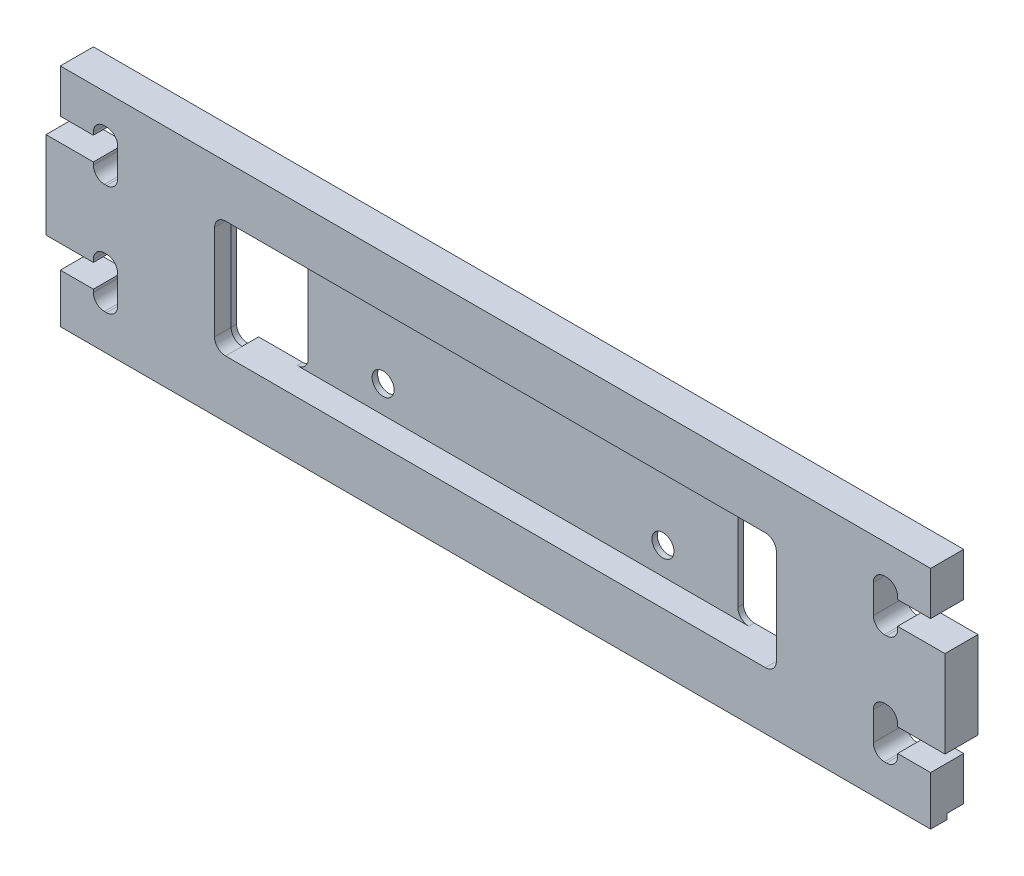
SolidWorks part; units mm, degrees
note: '?' marks a value the reader was unsure of.
ref_plane "Front Plane" through (0, 0, 0) normal (0, 0, 1) x (1, 0, 0)
ref_plane "Top Plane" through (0, 0, 0) normal (0, 1, 0) x (1, 0, 0)
ref_plane "Right Plane" through (0, 0, 0) normal (1, 0, 0) x (0, 0, -1)
sketch "Sketch1" plane through (0, 0, 0) normal (0, 0, 1) x (1, 0, 0)
  line L0 (-39.5, 0) -> (39.5, 0) construction
  line L1 (-39.5, 10) -> (39.5, 10)
  line L2 (-39.5, 10) -> (-39.5, -10)
  line L3 (-39.5, -10) -> (39.5, -10)
  line L4 (39.5, 10) -> (39.5, -10)
  line L5 (-39.5, 10) -> (39.5, -10) construction
  line L6 (-39.5, -10) -> (39.5, 10) construction
  line L7 (0, 10) -> (0, -10) construction
  line L9 (-40.8, -3.95) -> (-39.5, -3.95)
  line L10 (-40.8, -3.95) -> (-40.8, 3.95)
  line L11 (-40.8, 3.95) -> (-39.5, 3.95)
  line L12 (-39.5, -3.95) -> (-39.5, 3.95)
  line L13 (-40.8, -3.95) -> (-39.5, 3.95) construction
  line L14 (-40.8, 3.95) -> (-39.5, -3.95) construction
  line L16 (40.8, 3.95) -> (39.5, 3.95)
  line L17 (40.8, -3.95) -> (40.8, 3.95)
  line L18 (40.8, -3.95) -> (39.5, -3.95)
  line L19 (-39.5, 5) -> (39.5, 5) construction
  line L20 (-35.4, 7.3) -> (-35.4, 2.7) construction
  line L21 (-36.5, 3.95) -> (-39.5, 3.95)
  line L22 (-36.5, 3.95) -> (-36.5, 6.05)
  line L23 (-36.5, 6.05) -> (-39.5, 6.05)
  line L24 (-39.5, 3.95) -> (-39.5, 6.05)
  line L25 (-36.5, 3.95) -> (-39.5, 6.05) construction
  line L26 (-36.5, 6.05) -> (-39.5, 3.95) construction
  line L27 (-34.3, 7.3) -> (-36.5, 7.3)
  line L28 (-34.3, 7.3) -> (-34.3, 2.7)
  line L29 (-34.3, 2.7) -> (-36.5, 2.7)
  line L30 (-36.5, 7.3) -> (-36.5, 2.7)
  line L31 (-34.3, 7.3) -> (-36.5, 2.7) construction
  line L32 (-34.3, 2.7) -> (-36.5, 7.3) construction
  line L33 (-34.3, -7.3) -> (-36.5, -7.3)
  line L34 (-34.3, -7.3) -> (-34.3, -2.7)
  line L35 (-34.3, -2.7) -> (-36.5, -2.7)
  line L36 (-36.5, -7.3) -> (-36.5, -2.7)
  line L37 (-36.5, -3.95) -> (-39.5, -3.95)
  line L38 (-36.5, -6.05) -> (-39.5, -6.05)
  line L39 (36.5, 3.95) -> (39.5, 3.95)
  line L40 (36.5, 6.05) -> (39.5, 6.05)
  line L41 (36.5, 7.3) -> (36.5, 2.7)
  line L42 (34.3, 7.3) -> (36.5, 7.3)
  line L43 (34.3, 7.3) -> (34.3, 2.7)
  line L44 (34.3, 2.7) -> (36.5, 2.7)
  line L45 (34.3, -2.7) -> (36.5, -2.7)
  line L46 (34.3, -7.3) -> (34.3, -2.7)
  line L47 (34.3, -7.3) -> (36.5, -7.3)
  line L48 (36.5, -7.3) -> (36.5, -2.7)
  line L49 (36.5, -6.05) -> (39.5, -6.05)
  line L50 (36.5, -3.95) -> (39.5, -3.95)
  point P0 (0, 0)
  point P10 (-40.15, 0)
  point P15 (-38, 5)
  point P35 (-35.4, 5)
  dimension "D1" = 79
  dimension "D2" = 20
  dimension "D4" = 1.3
  dimension "D7" = 5
  dimension "D8" = 2.1
  dimension "D9" = 3
  dimension "D10" = 2.2
  dimension "D11" = 4.6
extrude "Base shape" add sketch "Sketch1" along normal blind 3
sketch "Sketch4" plane through (0, -10, 0) normal (0, -1, 0) x (1, 0, 0)
  line L0 (39.5, 3) -> (39.5, 0) construction
  line L1 (-39.5, 3) -> (39.5, 3)
  line L2 (-39.5, 3) -> (-39.5, 1.5)
  line L3 (-39.5, 1.5) -> (39.5, 1.5)
  line L4 (39.5, 3) -> (39.5, 1.5)
extrude "Floor lip" add sketch "Sketch4" along normal blind 0.5
sketch "Sketch6" plane through (0, 0, 0) normal (0, 0, -1) x (-1, 0, 0)
  line L0 (0, 0) -> (0, -10) construction
  line L1 (39.5, -10) -> (-39.5, -10) construction
  line L2 (-4, -10) -> (4, -10) construction
  line L3 (39.5, -10) -> (-39.5, -10) construction
  line L4 (-4, -9) -> (4, -9)
  line L5 (-4, -11) -> (4, -11)
  arc A0 (-4, -9) -> (-4, -11) centre (-4, -10) ccw
  arc A1 (4, -11) -> (4, -9) centre (4, -10) ccw
  point P9 (0, -10)
  dimension "D1" = 2
  dimension "D2" = 8
extrude "Nail cutout" cut sketch "Sketch6" against normal up to surface (1.5 mm away) up to face at (0, -10.25, 1.5)
sketch "Tap axis sketch" plane through (-40.8, 0, 0) normal (-1, 0, 0) x (0, 0, 1)
  line L0 (0, 6.05) -> (3, 3.95) construction
  line L1 (0, 6.05) -> (3, 6.05)
  line L2 (0, 6.05) -> (0, 3.95)
  line L3 (0, 3.95) -> (3, 3.95)
  line L4 (3, 6.05) -> (3, 3.95)
  line L5 (0, -3.95) -> (3, -6.05) construction
  line L6 (0, -3.95) -> (3, -3.95)
  line L7 (0, -3.95) -> (0, -6.05)
  line L8 (0, -6.05) -> (3, -6.05)
  line L9 (3, -3.95) -> (3, -6.05)
  point P6 (1.5, 5)
  point P13 (1.5, -5)
ref_axis "Tap axis top" through (-53.7846, 5, 1.5) along (1, 0, 0)?
ref_axis "Tap axis bottom" through (-54.2844, -5, 1.5) along (1, 0, 0)?
fillet "Mill fillets" radius 1 16 edges at (36.5, -7.3, 1.5) (36.5, 2.7, 1.5) (34.3, 2.7, 1.5) (34.3, -7.3, 1.5) (36.5, -2.7, 1.5) (36.5, 7.3, 1.5) (34.3, -2.7, 1.5) (34.3, 7.3, 1.5) (-36.5, -2.7, 1.5) (-34.3, -2.7, 1.5) (-34.3, -7.3, 1.5) (-36.5, -7.3, 1.5) (-36.5, 2.7, 1.5) (-34.3, 2.7, 1.5) (-34.3, 7.3, 1.5) (-36.5, 7.3, 1.5)
sketch "Sketch8" plane through (0, 0, 3) normal (0, 0, 1) x (1, 0, 0)
  line L0 (-40.8, 0) -> (40.8, 0) construction
  line L1 (-40.8, -3.95) -> (-40.8, 3.95) construction
  line L2 (40.8, -3.95) -> (40.8, 3.95) construction
  line L4 (-24.5, 5.3) -> (24.5, 5.3)
  line L5 (-25.5, 4.3) -> (-25.5, -4.3)
  line L6 (-24.5, -5.3) -> (24.5, -5.3)
  line L7 (25.5, 4.3) -> (25.5, -4.3)
  line L8 (-25.5, 5.3) -> (25.5, -5.3) construction
  line L9 (-25.5, -5.3) -> (25.5, 5.3) construction
  arc A0 (24.5, -5.3) -> (25.5, -4.3) centre (24.5, -4.3) ccw
  arc A1 (24.5, 5.3) -> (25.5, 4.3) centre (24.5, 4.3) cw
  arc A2 (-25.5, -4.3) -> (-24.5, -5.3) centre (-24.5, -4.3) ccw
  arc A3 (-24.5, 5.3) -> (-25.5, 4.3) centre (-24.5, 4.3) ccw
  point P6 (0, 0)
  dimension "D3" = 1
  dimension "D1" = 51
  dimension "D2" = 10.6
extrude "Led strip pocket" cut sketch "Sketch8" against normal offset from surface (2.5 mm away) 0.5 up to face at (0, -0.6712, 0)
sketch "Sketch9" plane through (0, 0, 0.5) normal (0, 0, 1) x (1, 0, 0)
  line L0 (-19.5, 5.3) -> (-19.5, -5.3)
  line L1 (0, 5.3) -> (0, -5.3) construction
  line L2 (19.5, 5.3) -> (19.5, -5.3)
  line L3 (-25.5, -2.828) -> (25.5, -2.828) construction
  line L4 (25.5, -4.3) -> (25.5, 4.3)
  line L5 (24.5, 5.3) -> (-24.5, 5.3)
  line L6 (-25.5, 4.3) -> (-25.5, -4.3)
  line L7 (-24.5, -5.3) -> (24.5, -5.3)
  line L8 (25.5, -4.3) -> (25.5, 4.3)
  line L9 (24.5, 5.3) -> (-24.5, 5.3)
  line L10 (-25.5, 4.3) -> (-25.5, -4.3)
  line L11 (-24.5, -5.3) -> (24.5, -5.3)
  circle A0 centre (-12.7, -2.828) radius 1
  circle A1 centre (12.7, -2.828) radius 1
  arc A4 (24.5, -5.3) -> (25.5, -4.3) centre (24.5, -4.3) ccw
  arc A5 (25.5, 4.3) -> (24.5, 5.3) centre (24.5, 4.3) ccw
  arc A6 (-24.5, 5.3) -> (-25.5, 4.3) centre (-24.5, 4.3) ccw
  arc A7 (-25.5, -4.3) -> (-24.5, -5.3) centre (-24.5, -4.3) ccw
  arc A8 (24.5, -5.3) -> (25.5, -4.3) centre (24.5, -4.3) ccw
  arc A9 (25.5, 4.3) -> (24.5, 5.3) centre (24.5, 4.3) ccw
  arc A10 (-24.5, 5.3) -> (-25.5, 4.3) centre (-24.5, 4.3) ccw
  arc A11 (-25.5, -4.3) -> (-24.5, -5.3) centre (-24.5, -4.3) ccw
  arc M13 (24.5, -5.3) -> (25.5, -4.3) centre (24.5, -4.3) ccw
  line M14 (25.5, -4.3) -> (25.5, 4.3)
  arc M15 (25.5, 4.3) -> (24.5, 5.3) centre (24.5, 4.3) ccw
  line M16 (24.5, 5.3) -> (-24.5, 5.3)
  arc M17 (-24.5, 5.3) -> (-25.5, 4.3) centre (-24.5, 4.3) ccw
  line M18 (-25.5, 4.3) -> (-25.5, -4.3)
  arc M19 (-25.5, -4.3) -> (-24.5, -5.3) centre (-24.5, -4.3) ccw
  line M20 (-24.5, -5.3) -> (24.5, -5.3)
  dimension "D4" = 2
  dimension "D2" = 6
  dimension "D3" = 8.128
  dimension "D5" = 25.4
  dimension "D1" = 0
extrude "Led strip cuts" cut sketch "Sketch9" against normal up to next contours L0 M16 M17 M18 M19 M20 | L2 M16 M20 M13 M14 M15 | A0 | A1
fillet "Led strip cut fillets" radius 1 4 edges at (19.5, -5.3, 0.25) (19.5, 5.3, 0.25) (-19.5, -5.3, 0.25) (-19.5, 5.3, 0.25)
sketch "Sketch23" plane through (0, 0, 0) normal (0, 0, -1) x (-1, 0, 0)
  line L0 (0, 12.1767) -> (0, -13.8681) construction
  line L1 (-25.5, -5.3) -> (-25.5, 5.3) construction
  line L2 (-25.5, 4.3) -> (-25.5, -4.3) construction
  line L3 (-26.5, -5.3) -> (-26.5, 5.3)
  line L4 (-24.5, -5.3) -> (-24.5, 5.3)
  line L5 (-20.5, 5.3) -> (-24.5, 5.3) construction
  line L6 (25.5, -5.3) -> (25.5, 5.3) construction
  line L7 (26.5, -5.3) -> (26.5, 5.3)
  line L8 (24.5, -5.3) -> (24.5, 5.3)
  arc A0 (-26.5, -5.3) -> (-24.5, -5.3) centre (-25.5, -5.3) ccw
  arc A1 (-24.5, 5.3) -> (-26.5, 5.3) centre (-25.5, 5.3) ccw
  arc A2 (26.5, -5.3) -> (24.5, -5.3) centre (25.5, -5.3) cw
  arc A3 (24.5, 5.3) -> (26.5, 5.3) centre (25.5, 5.3) cw
  point P7 (-25.5, 0)
  point P18 (25.5, 0)
  dimension "D1" = 2
extrude "LED PCB pads clearance slots" cut sketch "Sketch23" against normal blind 1.5
sketch "Sketch13" plane through (0, 0, 0) normal (0, 0, -1) x (-1, 0, 0)
  line L0 (0, 15.8648) -> (0, -21.9195) construction
  line L2 (-4.2, -6.3) -> (4.2, -6.3)
  line L3 (-5.2, -5.3) -> (-5.2, 6)
  line L4 (-4.2, 7) -> (4.2, 7)
  line L5 (5.2, -5.3) -> (5.2, 6)
  line L6 (-5.2, -6.3) -> (5.2, 7) construction
  line L7 (-5.2, 7) -> (5.2, -6.3) construction
  line L10 (39.5, 10) -> (-39.5, 10) construction
  arc A0 (-4.2, -6.3) -> (-5.2, -5.3) centre (-4.2, -5.3) cw
  arc A1 (4.2, -6.3) -> (5.2, -5.3) centre (4.2, -5.3) ccw
  arc A4 (5.2, 6) -> (4.2, 7) centre (4.2, 6) ccw
  arc A5 (-5.2, 6) -> (-4.2, 7) centre (-4.2, 6) cw
  point P1 (0, 0.35)
  dimension "D4" = 1
  dimension "D5" = 1
  dimension "D1" = 10.4
  dimension "D2" = 13.3
  dimension "D3" = 3
extrude "Bumper mount inner cut" [suppressed] cut sketch "Sketch13" against normal offset from surface (2.6 mm away) 0.4
sketch "Sketch14" [suppressed] plane through (0, 0, 0) normal (0, 0, -1) x (-1, 0, 0)
  line L1 (0, 12.9528) -> (0, -14.0841) construction
  line L2 (4.2, 7) -> (-4.2, 7) construction
  line L3 (-4.2, -6.3) -> (4.2, -6.3) construction
  line L4 (-11.7, 7) -> (11.7, 7)
  line L5 (-12.7, 6) -> (-12.7, -5.3)
  line L6 (-11.7, -6.3) -> (11.7, -6.3)
  line L7 (12.7, 6) -> (12.7, -5.3)
  line L8 (-12.7, 7) -> (12.7, -6.3) construction
  line L9 (-12.7, -6.3) -> (12.7, 7) construction
  arc A1 (11.7, -6.3) -> (12.7, -5.3) centre (11.7, -5.3) ccw
  arc A2 (-12.7, -5.3) -> (-11.7, -6.3) centre (-11.7, -5.3) ccw
  arc A3 (11.7, 7) -> (12.7, 6) centre (11.7, 6) cw
  arc A4 (-12.7, 6) -> (-11.7, 7) centre (-11.7, 6) cw
  point P6 (0, 0.35)
  dimension "D2" = 1
  dimension "D3" = 1
  dimension "D1" = 25.4
extrude "Bumper mount outer cut" [suppressed] cut sketch "Sketch14" against normal blind 1.6
sketch "Sketch15" [suppressed] plane through (0, 0, 1.6) normal (0, 0, -1) x (-1, 0, 0)
  line L0 (-12.7, 2.8) -> (12.7, 2.8) construction
  line L3 (0, 16.4744) -> (0, -20.0474) construction
  line L7 (-12.7, 6) -> (-12.7, -5.3) construction
  line L8 (12.7, -5.3) -> (12.7, 6) construction
  line L11 (-4.2, 7) -> (-11.7, 7) construction
  circle A0 centre (-9, 2.8) radius 1
  circle A1 centre (9, 2.8) radius 1
  dimension "D1" = 18
  dimension "D2" = 2
  dimension "D3" = 4.2
extrude "Bumper mount screw holes" [suppressed] cut sketch "Sketch15" against normal up to next
sketch "Sketch16" [suppressed] plane through (0, 0, 2.6) normal (0, 0, -1) x (-1, 0, 0)
  line L0 (-5.2, 1.1) -> (5.2, 1.1) construction
  line L3 (0, 7) -> (0, -4.8) construction
  line L4 (-2.5, 3) -> (2.5, 3)
  line L5 (-3.5, 2) -> (-3.5, 0.2)
  line L6 (-2.5, -0.8) -> (2.5, -0.8)
  line L7 (3.5, 2) -> (3.5, 0.2)
  line L8 (-3.5, 3) -> (3.5, -0.8) construction
  line L9 (-3.5, -0.8) -> (3.5, 3) construction
  line L11 (-5.2, 6) -> (-5.2, -5.3) construction
  line L13 (4.2, 7) -> (-4.2, 7) construction
  arc A0 (2.5, -0.8) -> (3.5, 0.2) centre (2.5, 0.2) ccw
  arc A1 (-3.5, 0.2) -> (-2.5, -0.8) centre (-2.5, 0.2) ccw
  arc A2 (-2.5, 3) -> (-3.5, 2) centre (-2.5, 2) ccw
  arc A3 (2.5, 3) -> (3.5, 2) centre (2.5, 2) cw
  point P6 (0, 1.1)
  dimension "D3" = 1
  dimension "D1" = 7
  dimension "D2" = 3.8
  dimension "D4" = 11.8
extrude "Bumper body cut" [suppressed] cut sketch "Sketch16" against normal up to next
hole_wizard "Bumper screw countersunks" [suppressed] positions "Sketch17" profile "Sketch18" countersink size "M2" standard "ANSI Metric"
sketch "Sketch17" plane through (0, 0, 3) normal (0, 0, 1) x (1, 0, 0)
  point P0 (9, 2.8)
  point P3 (-9, 2.8)
sketch "Sketch18" plane through (9, 2.8, 3) normal (1, 0, 0) x (0, -1, 0)
  line L0 (0, 0) -> (0, 3)
  line L1 (0, 3) -> (1, 3)
  line L2 (1, 3) -> (1, 1.3)
  line L3 (1, 1.3) -> (2, 0.3)
  line L4 (2, 0.3) -> (2, 0)
  line L6 (2, 0) -> (0, 0)
  line L7 (-1, 1.3) -> (-2, 0.3) construction
  line L11 (0, -6.35) -> (0, 107.95) construction
  dimension "Thru Hole Dia." = 2
  dimension "Thru Hole Depth" = 3
  dimension "C'Sink Dia." = 4
  dimension "C'Sink Angle" = 90
  dimension "Head Clearance" = 0.3
sketch "Sketch19" [suppressed] plane through (0, 0, 0) normal (0, 0, -1) x (-1, 0, 0)
  line L0 (0, 15.6498) -> (0, -12.9575) construction
  line L1 (39.5, 10) -> (-39.5, 10) construction
  line L2 (-2.2, 3) -> (2.2, 3)
  line L3 (-2.2, 3) -> (-2.2, 10)
  line L4 (-2.2, 10) -> (2.2, 10)
  line L5 (2.2, 3) -> (2.2, 10)
  line L6 (-2.2, 3) -> (2.2, 10) construction
  line L7 (-2.2, 10) -> (2.2, 3) construction
  line L8 (2.5, 3) -> (-2.5, 3) construction
  point P1 (0, 6.5)
  dimension "D1" = 4.4
extrude "Bumper insertion cut" [suppressed] cut sketch "Sketch19" against normal up to next
sketch "Sketch20" [suppressed] plane through (0, 0, 0) normal (0, 0, -1) x (-1, 0, 0)
  line L0 (-12.7, 6) -> (-12.7, -5.3) construction
  line L1 (-12.7, 4.55) -> (-32.7, 4.55)
  line L2 (-12.7, 4.55) -> (-12.7, -2)
  line L3 (-12.7, -2) -> (-32.7, -2)
  line L4 (-32.7, 4.55) -> (-32.7, -2)
  line L5 (-2.2, 10) -> (-39.5, 10) construction
  line L6 (-12.7, 4.55) -> (-19.25, -2) construction
  line L7 (-22.7, 4.55) -> (-22.7, -2) construction
  line L8 (-32.7, 1.275) -> (-12.7, 1.275) construction
  line L9 (0, 16.176) -> (0, -15.99) construction
  line L10 (12.7, 4.55) -> (12.7, -2)
  line L11 (12.7, -2) -> (32.7, -2)
  line L12 (32.7, 4.55) -> (32.7, -2)
  line L13 (12.7, 4.55) -> (32.7, 4.55)
  circle A0 centre (-13.4071, 3.8429) radius 1
  circle A1 centre (-31.9929, 3.8429) radius 1
  circle A2 centre (-13.4071, -1.2929) radius 1
  circle A3 centre (-31.9929, -1.2929) radius 1
  circle A4 centre (13.4071, 3.8429) radius 1
  circle A5 centre (13.4071, -1.2929) radius 1
  circle A6 centre (31.9929, -1.2929) radius 1
  circle A7 centre (31.9929, 3.8429) radius 1
  dimension "D5" = 2
  dimension "D1" = 20
  dimension "D2" = 5.45
  dimension "D3" = 6.55
  dimension "D4" = 45
extrude "Bumper switches cut" [suppressed] cut sketch "Sketch20" against normal up to next contours L1 L4 L3 L2 | A1 | A3 | A0 | A2 | L13 L12 L11 L10 | A4 | A5 | A6 | A7
sketch "Sketch21" [suppressed] plane through (0, 0, 0) normal (0, 0, -1) x (-1, 0, 0)
  line L0 (-14.1142, -2) -> (-31.2858, -2) construction
  line L1 (-32.7, -2) -> (-12.7, -2)
  line L2 (-32.7, -2) -> (-32.7, -6.3)
  line L3 (-32.7, -6.3) -> (-12.7, -6.3)
  line L4 (-12.7, -2) -> (-12.7, -6.3)
  line L5 (-12.7, -2) -> (-12.7, -5.3) construction
  line L6 (-11.7, -6.3) -> (-4.2, -6.3) construction
  line L7 (-32.7, 3.1358) -> (-32.7, -0.5858) construction
  line L8 (-12.7, -6.3) -> (-11.7, -6.3)
  line L9 (-32.7, -6.3) -> (-28.4, -2) construction
  line L10 (0, 14.2019) -> (0, -15.3745) construction
  line L11 (12.7, -6.3) -> (11.7, -6.3)
  line L12 (12.7, -2) -> (12.7, -6.3)
  line L13 (32.7, -2) -> (12.7, -2)
  line L14 (32.7, -2) -> (32.7, -6.3)
  line L15 (32.7, -6.3) -> (12.7, -6.3)
  arc A0 (-12.7, -5.3) -> (-11.7, -6.3) centre (-11.7, -5.3) ccw construction
  arc A1 (-12.7, -5.3) -> (-11.7, -6.3) centre (-11.7, -5.3) ccw
  circle A2 centre (-31.9929, -5.5929) radius 1
  arc A3 (-32.7, -0.5858) -> (-31.2858, -2) centre (-31.9929, -1.2929) ccw construction
  circle A4 centre (31.9929, -5.5929) radius 1
  arc A5 (12.7, -5.3) -> (11.7, -6.3) centre (11.7, -5.3) cw
  dimension "D1" = 45
extrude "Bumper switch mounts cut" [suppressed] cut sketch "Sketch21" against normal up to surface (1.6 mm away) contours A1 L4 L8 | L12 A5 L11 | A2 | A4
sketch "Front outer coordinate system sketch" [suppressed] plane through (0, 0, 3) normal (0, 0, 1) x (1, 0, 0)
  line L0 (-35.35, 7.35) -> (-35.35, 2.65) construction
  line L1 (-35.2, 7.35) -> (-35.5, 7.35) construction
  line L2 (-40.8, 3.95) -> (-40.8, 10) construction
  line L3 (-40.8, 10) -> (-39.5, 10) construction
  line L4 (-35.2, 2.65) -> (-35.5, 2.65) construction
  line L5 (0, 15.526) -> (0, -17.3739) construction
  line L6 (-51.2617, 0) -> (56.0692, 0) construction
  circle A0 centre (-35.35, 6.35) radius 1
  point P16 (-35.35, 6.35)
  point P22 (35.35, 6.35)
  point P24 (-35.35, -6.35)
  point P25 (35.35, -6.35)
  dimension "D1" = 2
sketch "Front inner coordinate system sketch" [suppressed] plane through (0, 0, 0) normal (0, 0, 1) x (1, 0, 0)
  line L0 (-40.8, -3.95) -> (-40.8, -10) construction
  line L1 (-40.8, -10) -> (-39.5, -10) construction
  line L3 (0, 19.9465) -> (0, -19.5427) construction
  line L4 (53.9633, 0) -> (-51.6097, 0) construction
sketch "Front deep inner pocket mill sketch" [suppressed] plane through (0, 0, 2.6) normal (0, 0, -1) x (-1, 0, 0)
  line L0 (-4.2, 7) -> (4.2, 7)
  line L12 (4.2, 7) -> (2.2, 7)
  line L13 (2.2, 7) -> (2.2, 3)
  line L14 (2.2, 3) -> (2.5, 3)
  line L15 (3.5, 2) -> (3.5, 0.2)
  line L16 (2.5, -0.8) -> (-2.5, -0.8)
  line L17 (-3.5, 0.2) -> (-3.5, 2)
  line L18 (-2.5, 3) -> (-2.2, 3)
  line L19 (-2.2, 3) -> (-2.2, 7)
  line L20 (-2.2, 7) -> (-4.2, 7)
  line L21 (-5.2, 6) -> (-5.2, -5.3)
  line L22 (-4.2, -6.3) -> (4.2, -6.3)
  line L23 (5.2, -5.3) -> (5.2, 6)
  line L33 (-5.2, 6) -> (-5.2, -5.3)
  line L34 (-4.2, -6.3) -> (4.2, -6.3)
  line L35 (5.2, -5.3) -> (5.2, 6)
  arc A8 (3.5, 2) -> (2.5, 3) centre (2.5, 2) ccw
  arc A9 (2.5, -0.8) -> (3.5, 0.2) centre (2.5, 0.2) ccw
  arc A10 (-3.5, 0.2) -> (-2.5, -0.8) centre (-2.5, 0.2) ccw
  arc A11 (-2.5, 3) -> (-3.5, 2) centre (-2.5, 2) ccw
  arc A12 (-4.2, 7) -> (-5.2, 6) centre (-4.2, 6) ccw
  arc A13 (-5.2, -5.3) -> (-4.2, -6.3) centre (-4.2, -5.3) ccw
  arc A14 (4.2, -6.3) -> (5.2, -5.3) centre (4.2, -5.3) ccw
  arc A15 (5.2, 6) -> (4.2, 7) centre (4.2, 6) ccw
  arc A20 (-4.2, 7) -> (-5.2, 6) centre (-4.2, 6) ccw
  arc A21 (-5.2, -5.3) -> (-4.2, -6.3) centre (-4.2, -5.3) ccw
  arc A22 (4.2, -6.3) -> (5.2, -5.3) centre (4.2, -5.3) ccw
  arc A23 (5.2, 6) -> (4.2, 7) centre (4.2, 6) ccw
  dimension "D1" = 0
sketch "Front shallow inner pocket mill sketch" [suppressed] plane through (0, 0, 1.6) normal (0, 0, -1) x (-1, 0, 0)
  line L2 (12.7, 4.55) -> (12.7, 6) construction
  line L7 (-12.7, 6) -> (-12.7, 4.55) construction
  line L16 (12.7, 4.55) -> (12.7, 6)
  line L21 (-12.7, 6) -> (-12.7, 4.55)
  line L42 (-32.7, -1) -> (-13.7, -1)
  line L43 (-12.7, 3.1358) -> (-12.7, -0.5858) construction
  line L47 (0, 16.1275) -> (0, -14.7685) construction
  line L53 (-31.2858, -6.3) -> (31.2858, -6.3)
  line L54 (-11.7, 7) -> (11.7, 7)
  line L55 (-12.7, 4.55) -> (-13.7, 4.55)
  line L56 (-13.7, 4.55) -> (-13.7, -1)
  line L58 (-22.7, -2) -> (-22.7, -1) construction
  line L59 (-31.2858, -2) -> (-14.1142, -2) construction
  line L60 (-12.7, 1.275) -> (-13.7, 1.275) construction
  line L61 (-32.7, -1) -> (-32.7, -4.8858)
  line L62 (12.7, 4.55) -> (13.7, 4.55)
  line L63 (13.7, 4.55) -> (13.7, -1)
  line L64 (32.7, -1) -> (13.7, -1)
  line L65 (32.7, -1) -> (32.7, -4.8858)
  arc A2 (12.7, 6) -> (11.7, 7) centre (11.7, 6) ccw construction
  arc A5 (31.2858, -6.3) -> (32.7, -4.8858) centre (31.9929, -5.5929) ccw construction
  arc A10 (-32.7, -4.8858) -> (-31.2858, -6.3) centre (-31.9929, -5.5929) ccw construction
  arc A13 (-11.7, 7) -> (-12.7, 6) centre (-11.7, 6) ccw construction
  arc A16 (12.7, 6) -> (11.7, 7) centre (11.7, 6) ccw
  arc A19 (31.2858, -6.3) -> (32.7, -4.8858) centre (31.9929, -5.5929) ccw
  arc A24 (-32.7, -4.8858) -> (-31.2858, -6.3) centre (-31.9929, -5.5929) ccw
  arc A27 (-11.7, 7) -> (-12.7, 6) centre (-11.7, 6) ccw
  dimension "D1" = 1
sketch "Rear outer coordinate system sketch" plane through (0, 0, 3) normal (0, 0, 1) x (1, 0, 0)
  line L0 (-39.5, 10) -> (-40.8, 10) construction
  line L1 (-40.8, 10) -> (-40.8, 3.95) construction
  line L2 (0, 16.5109) -> (0, -14.5399) construction
  line L3 (-9.6762, 0) -> (8.148, 0) construction
  line L4 (-35.4, 7.3) -> (-35.4, 2.7) construction
  line L5 (-35.3, 7.3) -> (-35.5, 7.3) construction
  line L6 (-35.3, 2.7) -> (-35.5, 2.7) construction
  line L7 (-34.3, 5) -> (-40.8, 5) construction
  line L8 (-34.3, 6.3) -> (-34.3, 3.7) construction
  circle A0 centre (-35.4, 6.3) radius 1
  arc A1 (-35.5, 7.3) -> (-36.5, 6.3) centre (-35.5, 6.3) ccw construction
  point P22 (-35.4, 6.3)
  point P27 (-35.4, 3.7)
  point P29 (-35.4, -6.3)
  point P30 (-35.4, -3.7)
  point P32 (35.4, 6.3)
  point P33 (35.4, 3.7)
  point P34 (35.4, -3.7)
  point P35 (35.4, -6.3)
sketch "Rear inner coordinate system sketch" plane through (0, 0, 0) normal (0, 0, -1) x (-1, 0, 0)
  line L0 (40.8, -3.95) -> (40.8, -10) construction
  line L1 (40.8, -10) -> (39.5, -10) construction
sketch "Rear pocket sketch" plane through (0, 0, 0.5) normal (0, 0, 1) x (1, 0, 0)
  line L5 (-24.5, -5.3) -> (24.5, -5.3)
  line L6 (-25.5, 4.3) -> (-25.5, -4.3)
  line L7 (24.5, 5.3) -> (-24.5, 5.3)
  line L8 (25.5, -4.3) -> (25.5, 4.3)
  line L9 (-24.5, -5.3) -> (24.5, -5.3)
  line L10 (-25.5, 4.3) -> (-25.5, -4.3)
  line L11 (24.5, 5.3) -> (-24.5, 5.3)
  line L12 (25.5, -4.3) -> (25.5, 4.3)
  arc A4 (24.5, -5.3) -> (25.5, -4.3) centre (24.5, -4.3) ccw
  arc A5 (-25.5, -4.3) -> (-24.5, -5.3) centre (-24.5, -4.3) ccw
  arc A6 (-24.5, 5.3) -> (-25.5, 4.3) centre (-24.5, 4.3) ccw
  arc A7 (25.5, 4.3) -> (24.5, 5.3) centre (24.5, 4.3) ccw
  arc A8 (24.5, -5.3) -> (25.5, -4.3) centre (24.5, -4.3) ccw
  arc A9 (-25.5, -4.3) -> (-24.5, -5.3) centre (-24.5, -4.3) ccw
  arc A10 (-24.5, 5.3) -> (-25.5, 4.3) centre (-24.5, 4.3) ccw
  arc A11 (25.5, 4.3) -> (24.5, 5.3) centre (24.5, 4.3) ccw
  dimension "D1" = 0
sketch "LED inner pockets sketch" plane through (0, 0, 0) normal (0, 0, -1) x (-1, 0, 0)
  line L0 (-20.5, 5.3) -> (-24.5, 5.3) construction
  line L1 (-19.5, -4.3) -> (-19.5, 4.3) construction
  line L2 (-24.5, -5.3) -> (-20.5, -5.3) construction
  line L3 (24.5, 5.3) -> (20.5, 5.3) construction
  line L4 (19.5, -4.3) -> (19.5, 4.3) construction
  line L5 (20.5, -5.3) -> (24.5, -5.3) construction
  line L6 (20.5, -5.3) -> (24.5, -5.3)
  line L7 (19.5, -4.3) -> (19.5, 4.3)
  line L8 (24.5, 5.3) -> (20.5, 5.3)
  line L9 (-24.5, -5.3) -> (-20.5, -5.3)
  line L10 (-19.5, -4.3) -> (-19.5, 4.3)
  line L11 (-20.5, 5.3) -> (-24.5, 5.3)
  line L12 (-25.5, -4.3) -> (-25.5, 4.3) construction
  line L13 (-25.5, -4.3) -> (-25.5, 4.3)
  line L14 (25.5, -4.3) -> (25.5, 4.3) construction
  line L15 (25.5, -4.3) -> (25.5, 4.3)
  arc A0 (19.5, -4.3) -> (20.5, -5.3) centre (20.5, -4.3) ccw construction
  arc A1 (-19.5, 4.3) -> (-20.5, 5.3) centre (-20.5, 4.3) ccw construction
  arc A2 (-20.5, -5.3) -> (-19.5, -4.3) centre (-20.5, -4.3) ccw construction
  arc A3 (20.5, 5.3) -> (19.5, 4.3) centre (20.5, 4.3) ccw construction
  arc A4 (19.5, -4.3) -> (20.5, -5.3) centre (20.5, -4.3) ccw
  arc A5 (20.5, 5.3) -> (19.5, 4.3) centre (20.5, 4.3) ccw
  arc A6 (-20.5, -5.3) -> (-19.5, -4.3) centre (-20.5, -4.3) ccw
  arc A7 (-19.5, 4.3) -> (-20.5, 5.3) centre (-20.5, 4.3) ccw
  arc A8 (-25.5, -4.3) -> (-24.5, -5.3) centre (-24.5, -4.3) ccw construction
  arc A9 (-24.5, 5.3) -> (-25.5, 4.3) centre (-24.5, 4.3) ccw construction
  arc A10 (-25.5, -4.3) -> (-24.5, -5.3) centre (-24.5, -4.3) ccw
  arc A11 (-24.5, 5.3) -> (-25.5, 4.3) centre (-24.5, 4.3) ccw
  arc A12 (24.5, -5.3) -> (25.5, -4.3) centre (24.5, -4.3) ccw construction
  arc A13 (25.5, 4.3) -> (24.5, 5.3) centre (24.5, 4.3) ccw construction
  arc A14 (24.5, -5.3) -> (25.5, -4.3) centre (24.5, -4.3) ccw
  arc A15 (25.5, 4.3) -> (24.5, 5.3) centre (24.5, 4.3) ccw
